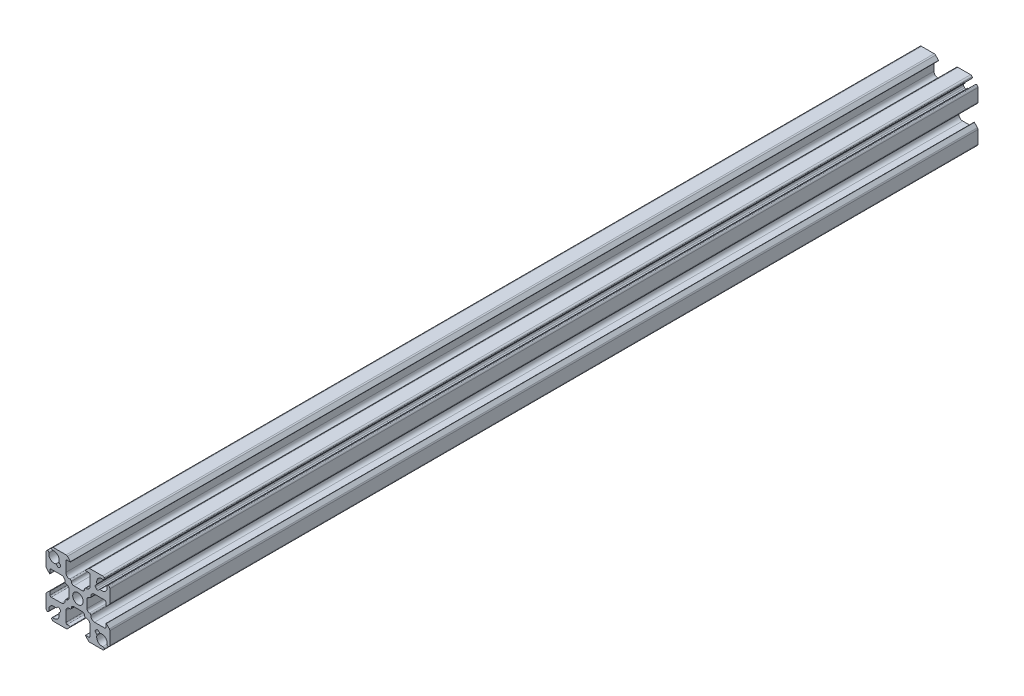
SolidWorks part; units mm, degrees
ref_plane "Front Plane" through (0, 0, 0) normal (0, 0, 1) x (1, 0, 0)
ref_plane "Top Plane" through (0, 0, 0) normal (0, 1, 0) x (1, 0, 0)
ref_plane "Right Plane" through (0, 0, 0) normal (1, 0, 0) x (0, 0, -1)
ref_plane "Plane1" through (0, 0, 0) normal (0, 0, -1) x (-1, 0, 0)
sketch "Sketch1" plane through (0, 0, 0) normal (0, 0, -1) x (-1, 0, 0)
  line L0 (-7.4885, 8.6199) -> (-6.9856, 8.117)
  line L1 (-6.9856, 7.4099) -> (-7.4099, 6.9856)
  line L2 (-8.117, 6.9856) -> (-8.6199, 7.4885)
  line L3 (-12.7, 9.7594) -> (-12.7, 4.7107)
  line L4 (-12.4803, 4.1803) -> (-11.2707, 2.9707)
  line L5 (-11.1, 3.0414) -> (-11.1, 4.325)
  line L6 (-10.6, 4.825) -> (-6.6, 4.825)
  line L7 (-5.1, 3.325) -> (-5.1, 3.15)
  line L8 (-3.6, 1.65) -> (-3.6, -1.65)
  line L9 (-5.1, -3.15) -> (-5.1, -3.325)
  line L10 (-6.6, -4.825) -> (-10.6, -4.825)
  line L11 (-11.1, -4.325) -> (-11.1, -3.0414)
  line L12 (-11.2707, -2.9707) -> (-12.4803, -4.1803)
  line L13 (-12.7, -4.7107) -> (-12.7, -9.7594)
  line L14 (-8.6199, -7.4885) -> (-8.117, -6.9856)
  line L15 (-7.4099, -6.9856) -> (-6.9856, -7.4099)
  line L16 (-6.9856, -8.117) -> (-7.4885, -8.6199)
  line L17 (-9.7594, -12.7) -> (-4.7107, -12.7)
  line L18 (-4.1803, -12.4803) -> (-2.9707, -11.2707)
  line L19 (-3.0414, -11.1) -> (-4.325, -11.1)
  line L20 (-4.825, -10.6) -> (-4.825, -6.6)
  line L21 (-3.325, -5.1) -> (-3.15, -5.1)
  line L22 (-1.65, -3.6) -> (1.65, -3.6)
  line L23 (3.15, -5.1) -> (3.325, -5.1)
  line L24 (4.825, -6.6) -> (4.825, -10.6)
  line L25 (4.325, -11.1) -> (3.0414, -11.1)
  line L26 (2.9707, -11.2707) -> (4.1803, -12.4803)
  line L27 (4.7107, -12.7) -> (9.7594, -12.7)
  line L28 (7.4885, -8.6199) -> (6.9856, -8.117)
  line L29 (6.9856, -7.4099) -> (7.4099, -6.9856)
  line L30 (8.117, -6.9856) -> (8.6199, -7.4885)
  line L31 (12.7, -9.7594) -> (12.7, -4.7107)
  line L32 (12.4803, -4.1803) -> (11.2707, -2.9707)
  line L33 (11.1, -3.0414) -> (11.1, -4.325)
  line L34 (10.6, -4.825) -> (6.6, -4.825)
  line L35 (5.1, -3.325) -> (5.1, -3.15)
  line L36 (3.6, -1.65) -> (3.6, 1.65)
  line L37 (5.1, 3.15) -> (5.1, 3.325)
  line L38 (6.6, 4.825) -> (10.6, 4.825)
  line L39 (11.1, 4.325) -> (11.1, 3.0414)
  line L40 (11.2707, 2.9707) -> (12.4803, 4.1803)
  line L41 (12.7, 4.7107) -> (12.7, 9.7594)
  line L42 (8.6199, 7.4885) -> (8.117, 6.9856)
  line L43 (7.4099, 6.9856) -> (6.9856, 7.4099)
  line L44 (6.9856, 8.117) -> (7.4885, 8.6199)
  line L45 (9.7594, 12.7) -> (4.7107, 12.7)
  line L46 (4.1803, 12.4803) -> (2.9707, 11.2707)
  line L47 (3.0414, 11.1) -> (4.325, 11.1)
  line L48 (4.825, 10.6) -> (4.825, 6.6)
  line L49 (3.325, 5.1) -> (3.15, 5.1)
  line L50 (1.65, 3.6) -> (-1.65, 3.6)
  line L51 (-3.15, 5.1) -> (-3.325, 5.1)
  line L52 (-4.825, 6.6) -> (-4.825, 10.6)
  line L53 (-4.325, 11.1) -> (-3.0414, 11.1)
  line L54 (-2.9707, 11.2707) -> (-4.1803, 12.4803)
  line L55 (-4.7107, 12.7) -> (-9.7594, 12.7)
  circle A0 centre (0, 0) radius 2.08
  arc A1 (-9.7594, 12.7) -> (-10.4266, 12.2927) centre (-9.7594, 11.95) ccw
  arc A2 (-10.4266, 12.2927) -> (-9.8933, 11.5721) centre (-9.9818, 12.0642) ccw
  arc A3 (-9.8933, 11.5721) -> (-7.5492, 8.8748) centre (-9.525, 9.525) cw
  arc A4 (-7.5492, 8.8748) -> (-7.4885, 8.6199) centre (-7.3118, 8.7967) ccw
  arc A5 (-6.9856, 8.117) -> (-6.9856, 7.4099) centre (-7.3392, 7.7635) cw
  arc A6 (-7.4099, 6.9856) -> (-8.117, 6.9856) centre (-7.7635, 7.3392) cw
  arc A7 (-8.6199, 7.4885) -> (-8.8748, 7.5492) centre (-8.7967, 7.3118) ccw
  arc A8 (-8.8748, 7.5492) -> (-11.5721, 9.8933) centre (-9.525, 9.525) cw
  arc A9 (-11.5721, 9.8933) -> (-12.2927, 10.4266) centre (-12.0642, 9.9818) ccw
  arc A10 (-12.2927, 10.4266) -> (-12.7, 9.7594) centre (-11.95, 9.7594) ccw
  arc A11 (-12.7, 4.7107) -> (-12.4803, 4.1803) centre (-11.95, 4.7107) ccw
  arc A12 (-11.2707, 2.9707) -> (-11.1, 3.0414) centre (-11.2, 3.0414) ccw
  arc A13 (-11.1, 4.325) -> (-10.6, 4.825) centre (-10.6, 4.325) cw
  arc A14 (-6.6, 4.825) -> (-5.1, 3.325) centre (-6.6, 3.325) cw
  arc A15 (-5.1, 3.15) -> (-4.6, 2.65) centre (-4.6, 3.15) ccw
  arc A16 (-4.6, 2.65) -> (-3.6, 1.65) centre (-4.6, 1.65) cw
  arc A17 (-3.6, -1.65) -> (-4.6, -2.65) centre (-4.6, -1.65) cw
  arc A18 (-4.6, -2.65) -> (-5.1, -3.15) centre (-4.6, -3.15) ccw
  arc A19 (-5.1, -3.325) -> (-6.6, -4.825) centre (-6.6, -3.325) cw
  arc A20 (-10.6, -4.825) -> (-11.1, -4.325) centre (-10.6, -4.325) cw
  arc A21 (-11.1, -3.0414) -> (-11.2707, -2.9707) centre (-11.2, -3.0414) ccw
  arc A22 (-12.4803, -4.1803) -> (-12.7, -4.7107) centre (-11.95, -4.7107) ccw
  arc A23 (-12.7, -9.7594) -> (-12.2927, -10.4266) centre (-11.95, -9.7594) ccw
  arc A24 (-12.2927, -10.4266) -> (-11.5721, -9.8933) centre (-12.0642, -9.9818) ccw
  arc A25 (-11.5721, -9.8933) -> (-8.8748, -7.5492) centre (-9.525, -9.525) cw
  arc A26 (-8.8748, -7.5492) -> (-8.6199, -7.4885) centre (-8.7967, -7.3118) ccw
  arc A27 (-8.117, -6.9856) -> (-7.4099, -6.9856) centre (-7.7635, -7.3392) cw
  arc A28 (-6.9856, -7.4099) -> (-6.9856, -8.117) centre (-7.3392, -7.7635) cw
  arc A29 (-7.4885, -8.6199) -> (-7.5492, -8.8748) centre (-7.3118, -8.7967) ccw
  arc A30 (-7.5492, -8.8748) -> (-9.8933, -11.5721) centre (-9.525, -9.525) cw
  arc A31 (-9.8933, -11.5721) -> (-10.4266, -12.2927) centre (-9.9818, -12.0642) ccw
  arc A32 (-10.4266, -12.2927) -> (-9.7594, -12.7) centre (-9.7594, -11.95) ccw
  arc A33 (-4.7107, -12.7) -> (-4.1803, -12.4803) centre (-4.7107, -11.95) ccw
  arc A34 (-2.9707, -11.2707) -> (-3.0414, -11.1) centre (-3.0414, -11.2) ccw
  arc A35 (-4.325, -11.1) -> (-4.825, -10.6) centre (-4.325, -10.6) cw
  arc A36 (-4.825, -6.6) -> (-3.325, -5.1) centre (-3.325, -6.6) cw
  arc A37 (-3.15, -5.1) -> (-2.65, -4.6) centre (-3.15, -4.6) ccw
  arc A38 (-2.65, -4.6) -> (-1.65, -3.6) centre (-1.65, -4.6) cw
  arc A39 (1.65, -3.6) -> (2.65, -4.6) centre (1.65, -4.6) cw
  arc A40 (2.65, -4.6) -> (3.15, -5.1) centre (3.15, -4.6) ccw
  arc A41 (3.325, -5.1) -> (4.825, -6.6) centre (3.325, -6.6) cw
  arc A42 (4.825, -10.6) -> (4.325, -11.1) centre (4.325, -10.6) cw
  arc A43 (3.0414, -11.1) -> (2.9707, -11.2707) centre (3.0414, -11.2) ccw
  arc A44 (4.1803, -12.4803) -> (4.7107, -12.7) centre (4.7107, -11.95) ccw
  arc A45 (9.7594, -12.7) -> (10.4266, -12.2927) centre (9.7594, -11.95) ccw
  arc A46 (10.4266, -12.2927) -> (9.8933, -11.5721) centre (9.9818, -12.0642) ccw
  arc A47 (9.8933, -11.5721) -> (7.5492, -8.8748) centre (9.525, -9.525) cw
  arc A48 (7.5492, -8.8748) -> (7.4885, -8.6199) centre (7.3118, -8.7967) ccw
  arc A49 (6.9856, -8.117) -> (6.9856, -7.4099) centre (7.3392, -7.7635) cw
  arc A50 (7.4099, -6.9856) -> (8.117, -6.9856) centre (7.7635, -7.3392) cw
  arc A51 (8.6199, -7.4885) -> (8.8748, -7.5492) centre (8.7967, -7.3118) ccw
  arc A52 (8.8748, -7.5492) -> (11.5721, -9.8933) centre (9.525, -9.525) cw
  arc A53 (11.5721, -9.8933) -> (12.2927, -10.4266) centre (12.0642, -9.9818) ccw
  arc A54 (12.2927, -10.4266) -> (12.7, -9.7594) centre (11.95, -9.7594) ccw
  arc A55 (12.7, -4.7107) -> (12.4803, -4.1803) centre (11.95, -4.7107) ccw
  arc A56 (11.2707, -2.9707) -> (11.1, -3.0414) centre (11.2, -3.0414) ccw
  arc A57 (11.1, -4.325) -> (10.6, -4.825) centre (10.6, -4.325) cw
  arc A58 (6.6, -4.825) -> (5.1, -3.325) centre (6.6, -3.325) cw
  arc A59 (5.1, -3.15) -> (4.6, -2.65) centre (4.6, -3.15) ccw
  arc A60 (4.6, -2.65) -> (3.6, -1.65) centre (4.6, -1.65) cw
  arc A61 (3.6, 1.65) -> (4.6, 2.65) centre (4.6, 1.65) cw
  arc A62 (4.6, 2.65) -> (5.1, 3.15) centre (4.6, 3.15) ccw
  arc A63 (5.1, 3.325) -> (6.6, 4.825) centre (6.6, 3.325) cw
  arc A64 (10.6, 4.825) -> (11.1, 4.325) centre (10.6, 4.325) cw
  arc A65 (11.1, 3.0414) -> (11.2707, 2.9707) centre (11.2, 3.0414) ccw
  arc A66 (12.4803, 4.1803) -> (12.7, 4.7107) centre (11.95, 4.7107) ccw
  arc A67 (12.7, 9.7594) -> (12.2927, 10.4266) centre (11.95, 9.7594) ccw
  arc A68 (12.2927, 10.4266) -> (11.5721, 9.8933) centre (12.0642, 9.9818) ccw
  arc A69 (11.5721, 9.8933) -> (8.8748, 7.5492) centre (9.525, 9.525) cw
  arc A70 (8.8748, 7.5492) -> (8.6199, 7.4885) centre (8.7967, 7.3118) ccw
  arc A71 (8.117, 6.9856) -> (7.4099, 6.9856) centre (7.7635, 7.3392) cw
  arc A72 (6.9856, 7.4099) -> (6.9856, 8.117) centre (7.3392, 7.7635) cw
  arc A73 (7.4885, 8.6199) -> (7.5492, 8.8748) centre (7.3118, 8.7967) ccw
  arc A74 (7.5492, 8.8748) -> (9.8933, 11.5721) centre (9.525, 9.525) cw
  arc A75 (9.8933, 11.5721) -> (10.4266, 12.2927) centre (9.9818, 12.0642) ccw
  arc A76 (10.4266, 12.2927) -> (9.7594, 12.7) centre (9.7594, 11.95) ccw
  arc A77 (4.7107, 12.7) -> (4.1803, 12.4803) centre (4.7107, 11.95) ccw
  arc A78 (2.9707, 11.2707) -> (3.0414, 11.1) centre (3.0414, 11.2) ccw
  arc A79 (4.325, 11.1) -> (4.825, 10.6) centre (4.325, 10.6) cw
  arc A80 (4.825, 6.6) -> (3.325, 5.1) centre (3.325, 6.6) cw
  arc A81 (3.15, 5.1) -> (2.65, 4.6) centre (3.15, 4.6) ccw
  arc A82 (2.65, 4.6) -> (1.65, 3.6) centre (1.65, 4.6) cw
  arc A83 (-1.65, 3.6) -> (-2.65, 4.6) centre (-1.65, 4.6) cw
  arc A84 (-2.65, 4.6) -> (-3.15, 5.1) centre (-3.15, 4.6) ccw
  arc A85 (-3.325, 5.1) -> (-4.825, 6.6) centre (-3.325, 6.6) cw
  arc A86 (-4.825, 10.6) -> (-4.325, 11.1) centre (-4.325, 10.6) cw
  arc A87 (-3.0414, 11.1) -> (-2.9707, 11.2707) centre (-3.0414, 11.2) ccw
  arc A88 (-4.1803, 12.4803) -> (-4.7107, 12.7) centre (-4.7107, 11.95) ccw
extrude "Boss-Extrude1" add sketch "Sketch1" against normal mid plane 345.1098
hole_wizard "Tap Drill for M6x1.0 Tap2" positions "Sketch3" profile "Sketch2" hole size "M6x1.0" standard "ANSI Metric" end condition through all
sketch "Sketch3" plane through (3.6, 0, 0) normal (1, 0, 0) x (0, 0, -1)
  point P0 (-132.5549, 0)
  point P3 (-12.5549, 0)
  point P6 (107.4451, 0)
sketch "Sketch2" plane through (3.6, 0, 132.5549) normal (0, 1, 0) x (0, 0, -1)
  line L0 (0, 0) -> (0, 16.3)
  line L1 (0, 16.3) -> (2.5, 16.3)
  line L2 (2.5, 16.3) -> (2.5, 0)
  line L5 (2.5, 0) -> (0, 0)
  line L11 (0, -6.35) -> (0, 107.95) construction
  dimension "Thru Hole Dia." = 5
  dimension "Thru Hole Depth" = 16.3
hole_wizard "Tap Drill for M6x1.0 Tap1" positions "Sketch5" profile "Sketch4" hole size "M6x1.0" standard "ANSI Metric" end condition through all
sketch "Sketch5" plane through (-3.6, 0, 0) normal (-1, 0, 0) x (0, 0, 1)
  point P0 (151.6049, 0)
  point P3 (31.6049, 0)
  point P6 (-88.3951, 0)
sketch "Sketch4" plane through (-3.6, 0, 151.6049) normal (0, 1, 0) x (0, 0, 1)
  line L0 (0, 0) -> (0, 16.3)
  line L1 (0, 16.3) -> (2.5, 16.3)
  line L2 (2.5, 16.3) -> (2.5, 0)
  line L5 (2.5, 0) -> (0, 0)
  line L11 (0, -6.35) -> (0, 107.95) construction
  dimension "Thru Hole Dia." = 5
  dimension "Thru Hole Depth" = 16.3
